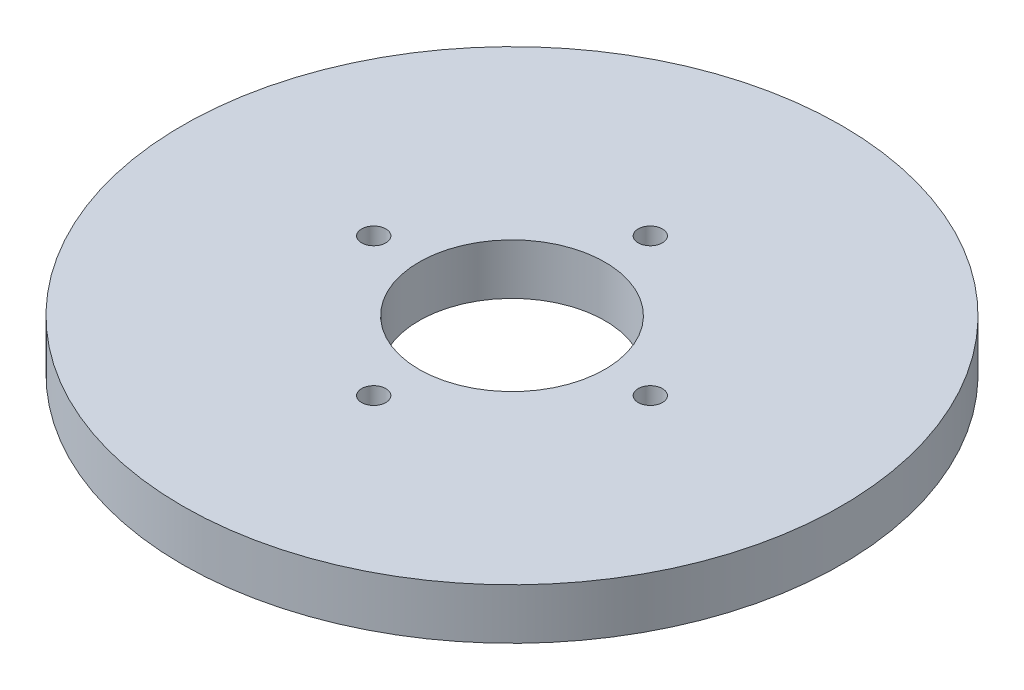
SolidWorks part; units mm, degrees
ref_plane "Front Plane" through (0, 0, 0) normal (0, 0, 1) x (1, 0, 0)
ref_plane "Top Plane" through (0, 0, 0) normal (0, 1, 0) x (1, 0, 0)
ref_plane "Right Plane" through (0, 0, 0) normal (1, 0, 0) x (0, 0, -1)
sketch "Sketch1" plane through (0, 0, 0) normal (0, 1, 0) x (1, 0, 0)
  circle A0 centre (0, 0) radius 97.5
  dimension "FLANGE_OD" = 195
extrude "Boss-Extrude1" add sketch "Sketch1" along normal blind 15
sketch "Sketch2" plane through (0, 0, 0) normal (0, 1, 0) x (1, 0, 0)
  circle A0 centre (0, 0) radius 27.5
  dimension "BORE_D" = 55
extrude "Cut-Extrude1" cut sketch "Sketch2" along normal through all
sketch "Sketch3" plane through (0, 15, 0) normal (0, 1, 0) x (1, 0, 0)
  circle A0 centre (0, 0) radius 40.9121 construction
  circle A1 centre (-40.9121, 0) radius 3.5896
  dimension "BOLT_D" = 7.1793
  dimension "BOLT_PCD" = 81.8242
extrude "Cut-Extrude2" cut sketch "Sketch3" against normal blind 9.6462
pattern_circular "CirPattern1" count 4 over 360 about axis through (0, 0, 0) along (0, 1, 0) of "Cut-Extrude2"
